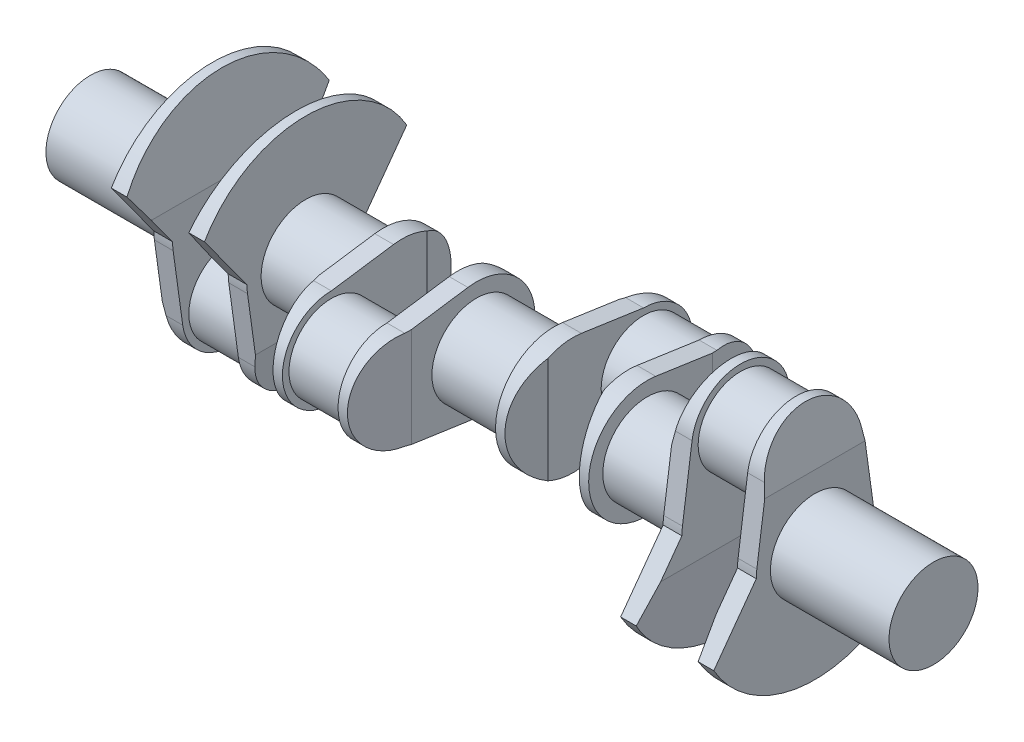
SolidWorks part; units mm, degrees
note: The reader was unsure of these and kept them because the rebuilt part matched: shared geometry of "Sketch1<2>", "Sketch1<3>", "Sketch6<2>", "Sketch9<3>", "Sketch9<4>".
ref_plane "Front Plane" through (0, 0, 0) normal (0, 0, 1) x (1, 0, 0)
ref_plane "Top Plane" through (0, 0, 0) normal (0, 1, 0) x (1, 0, 0)
ref_plane "Right Plane" through (0, 0, 0) normal (1, 0, 0) x (0, 0, -1)
sketch "Sketch1" plane through (0, 0, 0) normal (1, 0, 0) x (0, 0, -1)
  circle A0 centre (0, 0) radius 40
  dimension "D1" = 80
extrude "Boss-Extrude1" add sketch "Sketch1" along normal blind 106.62
sketch "Sketch2" plane through (0, 0, 0) normal (1, 0, 0) x (0, 0, -1)
  line L0 (43.5851, 69.5283) -> (52.203, 7.2203)
  line L1 (0, 0) -> (-90.9327, -52.5) construction
  line L2 (-90.9327, -52.5) -> (-52.7, 0)
  line L3 (0, 0) -> (90.9327, -52.5) construction
  line L4 (0, 0) -> (0, 63.5) construction
  line L5 (90.9327, -52.5) -> (52.7, 0)
  line L6 (-43.5851, 69.5283) -> (-52.203, 7.2203)
  arc A0 (52.7, 0) -> (52.203, 7.2203) centre (0, 0) ccw
  circle A1 centre (0, 63.5) radius 44
  arc A2 (-52.203, 7.2203) -> (-52.7, 0) centre (0, 0) ccw
  arc A3 (-90.9327, -52.5) -> (90.9327, -52.5) centre (0, 0) ccw
  circle A5 centre (0, 0) radius 40 construction
  dimension "D2" = 120
  dimension "D3" = 88
  dimension "D4" = 105
  dimension "D5" = 12.7
  dimension "D1" = 63.5
extrude "Boss-Extrude2" add sketch "Sketch2" against normal blind 16.86 contours L2 A3 L5 A0 L0 A1 L6 A2 | A1
sketch "Sketch3" plane through (-16.86, 0, 0) normal (-1, 0, 0) x (0, 0, 1)
  circle A0 centre (0, 63.5) radius 38.1
  dimension "D1" = 76.2
extrude "Boss-Extrude3" add sketch "Sketch3" along normal blind 50
pattern_linear "LPattern1" count 2 spacing 66.86 along (-1, 0, 0) of "Boss-Extrude2"
extrude "Boss-Extrude4" add sketch "Sketch1<2>" against normal blind 66.968 from surface
sketch "Sketch1<2>" plane through (0, 0, 0) normal (1, 0, 0) x (0, 0, -1) same geometry as "Sketch1"
sketch "Sketch4" plane through (-150.688, 0, 0) normal (-1, 0, 0) x (0, 0, 1)
  line L0 (0, 0) -> (-63.5, 0) construction
  line L1 (-63.5, 44) -> (-7.6023, 52.1488)
  line L2 (-63.5, -44) -> (-7.6023, -52.1488)
  circle A0 centre (0, 0) radius 52.7
  arc A1 (-63.5, 44) -> (-63.5, -44) centre (-63.5, 0) ccw
  dimension "D2" = 44
  dimension "D1" = 63.5
extrude "Boss-Extrude5" add sketch "Sketch4" along normal blind 16.86
sketch "Sketch5" plane through (-167.548, 0, 0) normal (-1, 0, 0) x (0, 0, 1)
  circle A0 centre (-63.5, 0) radius 38.1
  dimension "D1" = 76.2
extrude "Boss-Extrude6" add sketch "Sketch5" along normal blind 50
pattern_linear "LPattern2" count 2 spacing 66.86 along (-1, 0, 0) of "Boss-Extrude5"
extrude "Boss-Extrude7" add sketch "Sketch1<3>" against normal blind 69.86 from surface
sketch "Sketch1<3>" plane through (0, 0, 0) normal (1, 0, 0) x (0, 0, -1) same geometry as "Sketch1"
sketch "Sketch6" plane through (-304.268, 0, 0) normal (-1, 0, 0) x (0, 0, 1)
  point P0 (63.5511, 0)
  point P2 (-63.5, 0)
  line B0 (7.6533, -52.1488) -> (63.5511, -44)
  line B1 (63.5511, 44) -> (7.6533, 52.1488)
  arc B2 (63.5511, -44) -> (63.5511, 44) centre (63.5511, 0) ccw
  arc B3 (7.6533, 52.1488) -> (7.6533, -52.1488) centre (0.0511, 0) ccw
sketch_block_instance "Block1-1"
sketch_block "Block1"
extrude "Boss-Extrude8" add sketch "Sketch6" along normal blind 16.86
sketch "Sketch7" plane through (-321.128, 0, 0) normal (-1, 0, 0) x (0, 0, 1)
  circle A0 centre (63.5511, 0) radius 38.1
  dimension "D1" = 76.2
extrude "Boss-Extrude9" add sketch "Sketch7" along normal blind 50
extrude "Boss-Extrude10" add sketch "Sketch6<2>" along normal blind 16.86 from surface at 66.86 starting at face at (-371.128, 0, 101.6511)
sketch "Sketch6<2>" plane through (-304.268, 0, 0) normal (-1, 0, 0) x (0, 0, 1) same geometry as "Sketch6"
sketch "Sketch8" plane through (-387.988, 0, 0) normal (-1, 0, 0) x (0, 0, 1)
  circle A0 centre (0, 0) radius 40
  dimension "D1" = 80
extrude "Boss-Extrude11" add sketch "Sketch8" along normal blind 69.86
sketch "Sketch9" plane through (-457.848, 0, 0) normal (-1, 0, 0) x (0, 0, 1)
  circle A1 centre (0, 0) radius 40
  circle A2 centre (0, 0) radius 40
  point P0 (0, -63.5)
  point P5 (0, 0)
  line B0 (-90.9327, 52.5) -> (-52.7, 0)
  line B1 (-52.203, -7.2203) -> (-43.5851, -69.5283)
  line B2 (43.5851, -69.5283) -> (52.203, -7.2203)
  line B3 (52.7, 0) -> (90.9327, 52.5)
  arc B4 (-52.7, 0) -> (-52.203, -7.2203) centre (0, 0) ccw
  arc B5 (-43.5851, -69.5283) -> (43.5851, -69.5283) centre (0, -63.5) ccw
  arc B6 (52.203, -7.2203) -> (52.7, 0) centre (0, 0) ccw
  arc B7 (90.9327, 52.5) -> (-90.9327, 52.5) centre (0, 0) ccw
  circle M10 centre (0, 0) radius 40
  dimension "D1" = 0
sketch_block_instance "Block2-1"
sketch_block "Block2"
extrude "Boss-Extrude12" add sketch "Sketch9" along normal blind 16.86 contours M10 | B3 B7 B0 B4 B1 B5 B2 B6 M10
sketch "Sketch10" plane through (-474.708, 0, 0) normal (-1, 0, 0) x (0, 0, 1)
  circle A0 centre (0, -63.5) radius 38.1
  dimension "D1" = 76.2
extrude "Boss-Extrude13" add sketch "Sketch10" along normal blind 50
extrude "Boss-Extrude14" add sketch "Sketch9<3>" along normal blind 16.86 from surface at 66.86 contours M10 | B3 B7 B0 B4 B1 B5 B2 B6 M10 starting at face at (-524.708, -63.5, 38.1)
sketch "Sketch9<3>" plane through (-457.848, 0, 0) normal (-1, 0, 0) x (0, 0, 1) same geometry as "Sketch9"
extrude "Boss-Extrude15" add sketch "Sketch9<4>" along normal blind 109.72 from surface at 83.72 starting at face at (-541.568, -4.2483, 0)
sketch "Sketch9<4>" plane through (-457.848, 0, 0) normal (-1, 0, 0) x (0, 0, 1) same geometry as "Sketch9"
sketch "Sketch11" plane through (0, 0, 0) normal (0, 0, 1) x (1, 0, 0)
  line L0 (-533.138, 105) -> (-524.708, 105)
  line L1 (-524.708, 105) -> (-541.568, 105) construction
  line L2 (-524.708, 105) -> (-524.708, 26.25)
  line L3 (-524.708, 52.5) -> (-524.708, 0) construction
  line L4 (-524.708, 26.25) -> (-533.138, 105)
  line L5 (-474.708, 105) -> (-466.278, 105)
  line L6 (-474.708, 105) -> (-474.708, 52.5) construction
  line L7 (-457.848, 105) -> (-474.708, 105) construction
  line L8 (-466.278, 105) -> (-474.708, 26.25)
  line L9 (-474.708, 0) -> (-474.708, 52.5) construction
  line L10 (-474.708, 26.25) -> (-474.708, 105)
  line L12 (-541.568, -107.5) -> (-524.708, -107.5) construction
  line L15 (-541.568, -107.5) -> (-533.138, -107.5)
  line L16 (-466.278, -107.5) -> (-457.848, -107.5)
  line L17 (-474.708, -107.5) -> (-457.848, -107.5) construction
  line L21 (-75.29, -105) -> (-66.86, -26.25)
  line L22 (-83.72, -105) -> (-66.86, -105) construction
  line L23 (-66.86, -52.5) -> (-66.86, 0) construction
  line L24 (-66.86, -26.25) -> (-66.86, -105)
  line L25 (-66.86, -105) -> (-66.86, -52.5) construction
  line L26 (-66.86, -105) -> (-75.29, -105)
  line L27 (-16.86, -26.25) -> (-8.43, -105)
  line L28 (-16.86, -52.5) -> (-16.86, 0) construction
  line L29 (-16.86, -105) -> (0, -105) construction
  line L30 (-8.43, -105) -> (-16.86, -105)
  line L31 (-16.86, -105) -> (-16.86, -26.25)
  line L32 (-8.43, 107.5) -> (0, 107.5)
  line L33 (0, 107.5) -> (-16.86, 107.5) construction
  line L34 (0, 107.5) -> (0, 58.5)
  line L35 (0, 69.5283) -> (0, 107.5) construction
  line L36 (0, 58.5) -> (-8.43, 107.5)
  line L37 (-83.72, 107.5) -> (-75.29, 107.5)
  line L38 (-66.86, 107.5) -> (-83.72, 107.5) construction
  line L39 (-75.29, 107.5) -> (-83.72, 58.5)
  line L40 (-83.72, 107.5) -> (-83.72, 69.5283) construction
  line L41 (-83.72, 58.5) -> (-83.72, 107.5)
  line L42 (-541.568, -107.5) -> (-541.568, -58.5)
  line L43 (-541.568, -7.2203) -> (-541.568, -69.5283) construction
  line L44 (-541.568, -58.5) -> (-533.138, -107.5)
  line L45 (-466.278, -107.5) -> (-457.848, -58.5)
  line L46 (-457.848, -69.5283) -> (-457.848, -7.2203) construction
  line L47 (-457.848, -58.5) -> (-457.848, -107.5)
  dimension "D1" = 49
  dimension "D2" = 49
  dimension "D3" = 49
  dimension "D4" = 49
extrude "Cut-Extrude1" cut sketch "Sketch11" against normal through all both and the other way through all
sketch "Sketch12" plane through (0, 0, 0) normal (0, 1, 0) x (1, 0, 0)
  line L0 (-379.558, -107.5511) -> (-387.988, -58.5511)
  line L1 (-387.988, -107.5511) -> (-371.128, -107.5511) construction
  line L2 (-387.988, -7.6533) -> (-387.988, -63.5511) construction
  line L3 (-387.988, -58.5511) -> (-387.988, -107.5511)
  line L4 (-387.988, -107.5511) -> (-379.558, -107.5511)
  line L6 (-304.268, -107.5511) -> (-304.268, -58.5511)
  line L7 (-304.268, -40) -> (-304.268, 40) construction
  line L9 (-304.268, -107.5511) -> (-312.698, -107.5511)
  line L10 (-321.128, -107.5511) -> (-304.268, -107.5511) construction
  line L11 (-312.698, -107.5511) -> (-304.268, -58.5511)
  line L12 (-379.558, 52.6489) -> (-371.128, 52.6489)
  line L13 (-371.128, 52.6489) -> (-387.988, 52.6489) construction
  line L14 (-371.128, -7.6533) -> (-371.128, 52.6489) construction
  line L15 (-371.128, 52.6489) -> (-371.128, 22.4978)
  line L16 (-371.128, 22.4978) -> (-379.558, 52.6489)
  line L17 (-312.698, 52.6489) -> (-321.128, 22.4978)
  line L18 (-304.268, 52.6489) -> (-321.128, 52.6489) construction
  line L19 (-321.128, 52.6489) -> (-321.128, -7.6533) construction
  line L20 (-321.128, 22.4978) -> (-321.128, 52.6489)
  line L21 (-321.128, 52.6489) -> (-312.698, 52.6489)
  line L22 (-159.118, 107.5) -> (-150.688, 107.5)
  line L23 (-150.688, 107.5) -> (-167.548, 107.5) construction
  line L24 (-150.688, 63.5) -> (-150.688, 107.5) construction
  line L25 (-159.118, 107.5) -> (-150.688, 58.5)
  line L26 (-150.688, 58.5) -> (-150.688, 107.5)
  line L27 (-225.978, 107.5) -> (-234.408, 107.5)
  line L28 (-217.548, 107.5) -> (-234.408, 107.5) construction
  line L29 (-234.408, 107.5) -> (-234.408, 58.5)
  line L30 (-234.408, 107.5) -> (-234.408, 63.5) construction
  line L31 (-234.408, 58.5) -> (-225.978, 107.5)
  line L32 (-217.548, -52.7) -> (-225.978, -52.7)
  line L33 (-234.408, -52.7) -> (-217.548, -52.7) construction
  line L34 (-225.978, -52.7) -> (-217.548, -22.5489)
  line L35 (-217.548, -52.7) -> (-217.548, 7.6023) construction
  line L36 (-217.548, -22.5489) -> (-217.548, -52.7)
  line L37 (-159.118, -52.7) -> (-167.548, -22.5489)
  line L38 (-167.548, -52.7) -> (-150.688, -52.7) construction
  line L39 (-167.548, 7.6023) -> (-167.548, -52.7) construction
  line L40 (-167.548, -22.5489) -> (-167.548, -52.7)
  line L41 (-167.548, -52.7) -> (-159.118, -52.7)
  dimension "D1" = 49
  dimension "D2" = 49
  dimension "D3" = 49
  dimension "D4" = 49
extrude "Cut-Extrude2" cut sketch "Sketch12" against normal through all both and the other way through all
